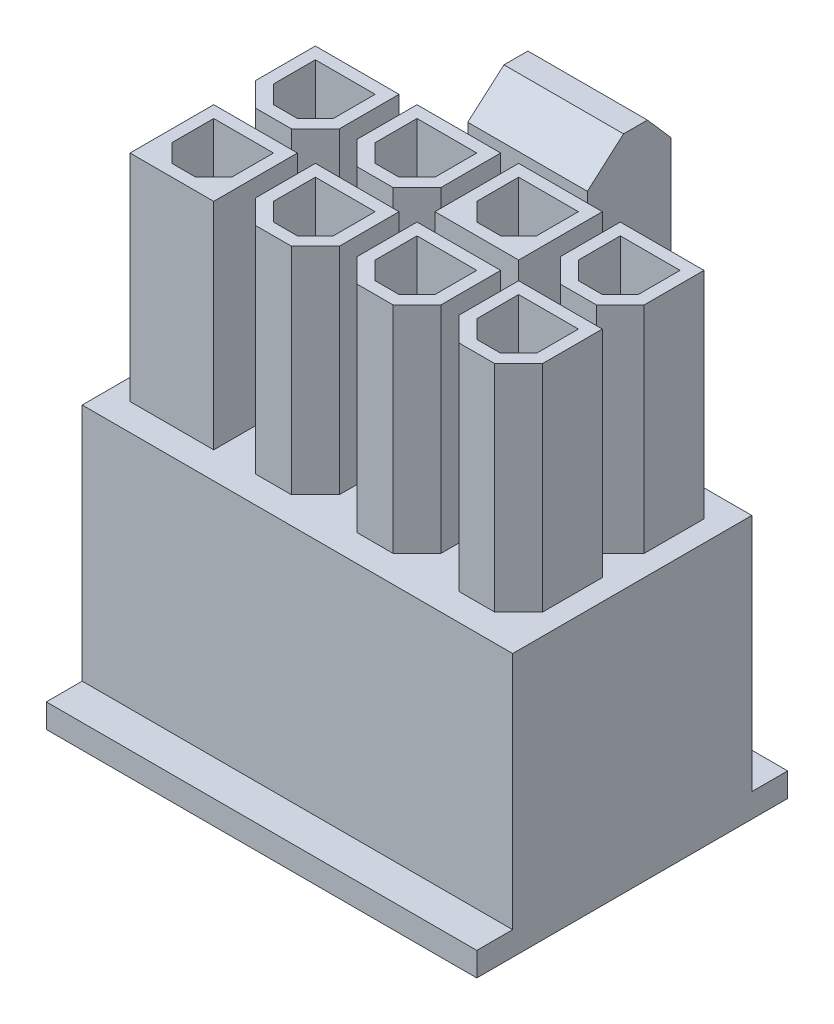
SolidWorks part; units mm, degrees
ref_plane "Ebene vorne" through (0, 0, 0) normal (0, 0, 1) x (1, 0, 0)
ref_plane "Ebene oben" through (0, 0, 0) normal (0, 1, 0) x (1, 0, 0)
ref_plane "Ebene rechts" through (0, 0, 0) normal (1, 0, 0) x (0, 0, -1)
sketch "Skizze1" plane through (0, 0, 0) normal (1, 0, 0) x (0, 0, -1)
  line L1 (5, 0) -> (-5, 0)
  line L2 (5, 0) -> (5, 11)
  line L3 (5, 11) -> (-5, 11)
  line L4 (-5, 0) -> (-5, 11)
  point P4 (0, 0)
  dimension "D1" = 10
  dimension "D2" = 11
extrude "Aufsatz-Linear austragen1" add sketch "Skizze1" along normal mid plane 18
sketch "Skizze2" plane through (0, 0, 0) normal (1, 0, 0) x (0, 0, -1)
  line L0 (0, 0) -> (0, 11) construction
  line L1 (-5, 0) -> (-6.5, 0)
  line L2 (-5, 0) -> (-5, 1)
  line L3 (-5, 1) -> (-6.5, 1)
  line L4 (-6.5, 0) -> (-6.5, 1)
  line L5 (5, 11) -> (-5, 11) construction
  line L6 (6.5, 0) -> (6.5, 1)
  line L7 (5, 1) -> (6.5, 1)
  line L8 (5, 0) -> (5, 1)
  line L9 (5, 0) -> (6.5, 0)
  dimension "D1" = 1.5
  dimension "D2" = 1
extrude "Aufsatz-Linear austragen2" add sketch "Skizze2" along normal mid plane 18
sketch "Skizze3" plane through (0, 0, 0) normal (1, 0, 0) x (0, 0, -1)
  line L0 (5, 11) -> (5.5717, 11)
  line L1 (7.5, 8.198) -> (7.5, 5.198)
  line L2 (7.5, 5.198) -> (8.5, 4)
  line L3 (8.5, 4) -> (8.5, 2)
  line L4 (8.5, 2) -> (6.5, 2)
  line L5 (6.5, 2) -> (6.5, 8)
  line L6 (6.5, 8) -> (5, 8)
  line L7 (5, 1) -> (5, 11) construction
  line L8 (5, 11) -> (5, 8)
  line L9 (-6.5, 0) -> (6.5, 0) construction
  arc A0 (5.5717, 11) -> (6.5359, 9.599) centre (7.0717, 11) ccw
  arc A1 (6.5359, 9.599) -> (7.5, 8.198) centre (6, 8.198) cw
  dimension "D5" = 1.5
  dimension "D1" = 2
  dimension "D2" = 1
  dimension "D3" = 2
  dimension "D4" = 2
  dimension "D6" = 3
  dimension "D7" = 1.5
  dimension "D8" = 3
extrude "Aufsatz-Linear austragen3" add sketch "Skizze3" along normal mid plane 8
sketch "Skizze4" plane through (0, 0, 0) normal (0, -1, 0) x (1, 0, 0)
  line L0 (9, -5) -> (-9, -5) construction
  line L1 (-2.5, -5) -> (2.5, -5)
  line L2 (-2.5, -5) -> (-2.5, -6.5)
  line L3 (-2.5, -6.5) -> (2.5, -6.5)
  line L4 (2.5, -5) -> (2.5, -6.5)
  line L5 (9, -6.5) -> (-9, -6.5) construction
  line L6 (0, -5) -> (0, 0) construction
  line L7 (-4, -6.5) -> (-4, -8.5) construction
  dimension "D1" = 1.5
extrude "Schnitt-Linear austragen1" cut sketch "Skizze4" against normal through all
sketch "Skizze5" plane through (0, 0, 0) normal (1, 0, 0) x (0, 0, -1)
  line L0 (8.1235, 4.451) -> (8.1235, 19.8707)
  line L1 (8.5, 4) -> (7.5, 5.198) construction
  line L2 (8.1235, 19.8707) -> (7.1363, 21)
  line L3 (7.1363, 21) -> (6.1363, 21)
  line L4 (6.1363, 21) -> (4.6235, 19.6776)
  line L5 (4.6235, 19.6776) -> (4.6235, 17.6776)
  line L6 (4.6235, 17.6776) -> (6.1235, 17.6776)
  line L7 (6.1235, 17.6776) -> (6.5, 8)
  line L8 (6.5, 8) -> (6.5, 2)
  line L9 (6.5, 2) -> (8.1235, 4.451)
  line L10 (5, 11) -> (-5, 11) construction
  dimension "D1" = 3.5
  dimension "D2" = 1.5
  dimension "D3" = 1
  dimension "D4" = 10
  dimension "D5" = 2
  dimension "D6" = 2.0093
  dimension "D7" = 1.5
extrude "Aufsatz-Linear austragen4" add sketch "Skizze5" along normal mid plane 5
sketch "Skizze6" plane through (0, 0, 0) normal (0, -1, 0) x (1, 0, 0)
  line L0 (-9, 6.5) -> (-9, -6.5) construction
  line L1 (-8.25, -4) -> (-4.5, -4)
  line L2 (-8.25, -4) -> (-8.25, -0.25)
  line L3 (-8.25, -0.25) -> (-4.5, -0.25)
  line L4 (-4.5, -4) -> (-4.5, -0.25)
  line L5 (-2.5, -5) -> (-9, -5) construction
  dimension "D1" = 0.75
  dimension "D2" = 1
  dimension "D3" = 3.75
extrude "Schnitt-Linear austragen2" cut sketch "Skizze6" against normal blind 10
pattern_linear "Lineares Muster1" count 4 spacing 4.25 along (1, 0, 0) count 2 spacing 4.25 along (0, 0, 1) of "Schnitt-Linear austragen2"
sketch "Skizze7" plane through (0, 11, 0) normal (0, 1, 0) x (1, 0, 0)
  line L1 (-4.5, -0.25) -> (-8.25, -4) construction
  line L2 (-8.25, -0.25) -> (-4.5, -4) construction
  line L4 (-8.125, -0.375) -> (-4.625, -0.375)
  line L6 (-8.125, -0.375) -> (-8.125, -3.875)
  line L8 (-8.125, -3.875) -> (-4.625, -3.875)
  line L10 (-4.625, -0.375) -> (-4.625, -3.875)
  line L11 (-8.125, -0.375) -> (-4.625, -3.875) construction
  point P4 (-6.375, -2.125)
  dimension "D1" = 3.5
extrude "Aufsatz-Linear austragen5" add sketch "Skizze7" along normal blind 9
pattern_linear "Lineares Muster2" count 3 spacing 4.25 along (1, 0, 0) count 2 spacing 4.25 along (0, 0, -1) skipping (0, 1), (1, 0), (1, 1), (2, 0) of "Aufsatz-Linear austragen5"
sketch "Skizze10" plane through (0, 11, 0) normal (0, 1, 0) x (1, 0, 0)
  line L0 (-8.25, 4) -> (-4.5, 0.25) construction
  line L1 (-4.5, 4) -> (-8.25, 0.25) construction
  line L3 (-4.625, 1.375) -> (-5.625, 0.375)
  line L5 (-5.625, 0.375) -> (-7.125, 0.375)
  line L6 (-4.625, 1.375) -> (-4.625, 3.875)
  line L7 (-4.625, 3.875) -> (-8.125, 3.875)
  line L8 (-8.125, 1.375) -> (-8.125, 3.875)
  line L9 (-4.625, 0.375) -> (-8.125, 3.875) construction
  line L10 (-4.625, 3.875) -> (-8.125, 0.375) construction
  line L11 (-7.125, 0.375) -> (-8.125, 1.375)
  point P4 (-6.375, 2.125)
  dimension "D1" = 3.5
extrude "Aufsatz-Linear austragen7" add sketch "Skizze10" along normal up to surface (9 mm away) up to face at (-6.375, 20, 2.125)
pattern_linear "Lineares Muster4" count 4 spacing 4.25 along (1, 0, 0) count 2 spacing 4.25 along (0, 0, 1) skipping (0, 1), (2, 0) of "Aufsatz-Linear austragen7"
sketch "Skizze12" plane through (0, 20, 0) normal (0, 1, 0) x (1, 0, 0)
  line L16 (-8.25, 2.125) -> (-4.5, 2.125) construction
  line L17 (-6.375, 4) -> (-6.375, 0.25) construction
  line L18 (-8.25, 4) -> (-3.0668, -1.1832) construction
  line L19 (-5.875, 0.875) -> (-5.125, 1.625)
  line L20 (-7.625, 3.375) -> (-5.125, 3.375)
  line L21 (-7.625, 3.375) -> (-7.625, 1.625)
  line L22 (-6.875, 0.875) -> (-5.875, 0.875)
  line L23 (-5.125, 3.375) -> (-5.125, 1.625)
  line L24 (-7.625, 3.375) -> (-5.125, 0.875) construction
  line L25 (-7.625, 0.875) -> (-5.125, 3.375) construction
  line L26 (-7.625, 1.625) -> (-6.875, 0.875)
  line L27 (-4.5, 4) -> (-4.5, 0.25) construction
  line L28 (-8.25, 0.25) -> (-8.25, 4) construction
  line L29 (-8.25, 4) -> (-4.5, 4) construction
  line L30 (-4.5, 0.25) -> (-8.25, 0.25) construction
  point P35 (-6.375, 2.125)
  dimension "D1" = 2.5
  dimension "D3" = 0.75
  dimension "D4" = 0.75
  dimension "D5" = 0.75
  dimension "D6" = 0.75
  dimension "D7" = 2.5
extrude "Schnitt-Linear austragen4" cut sketch "Skizze12" against normal through all
pattern_linear "Lineares Muster6" count 4 spacing 4.25 along (1, 0, 0) count 2 spacing 4.25 along (0, 0, 1) of "Schnitt-Linear austragen4"
sketch "草图2" plane through (0, 10, 0) normal (0, -1, 0) x (-1, 0, 0)
  point P8 (-6.375, -2.125)
  point P9 (-6.375, 2.125)
  point P10 (-2.125, 2.125)
  point P11 (-2.125, -2.125)
  point P12 (2.125, -2.125)
  point P13 (2.125, 2.125)
  point P14 (6.375, -2.125)
  point P15 (6.375, 2.125)
other "连接点1" parameters "直径"=2, "端头长度"=10
ref_axis "基准轴9" through (6.375, 0, -2.125) along (0, 1, 0)
other "连接点2" parameters "直径"=2, "端头长度"=10
ref_axis "基准轴10" through (6.375, 0, 2.125) along (0, 1, 0)
other "连接点3" parameters "直径"=2, "端头长度"=10
ref_axis "基准轴11" through (2.125, 0, 2.125) along (0, 1, 0)
other "连接点4" parameters "直径"=2, "端头长度"=10
ref_axis "基准轴12" through (2.125, 0, -2.125) along (0, 1, 0)
other "连接点5" parameters "直径"=2, "端头长度"=10
ref_axis "基准轴13" through (-2.125, 0, -2.125) along (0, 1, 0)
other "连接点6" parameters "直径"=2, "端头长度"=10
ref_axis "基准轴14" through (-2.125, 0, 2.125) along (0, 1, 0)
other "连接点7" parameters "直径"=2, "端头长度"=10
ref_axis "基准轴15" through (-6.375, 0, -2.125) along (0, 1, 0)
other "连接点8" parameters "直径"=2, "端头长度"=10
ref_axis "基准轴16" through (-6.375, 0, 2.125) along (0, 1, 0)
ref_axis "B2" through (6.375, 10, -2.125) along (0, -1, 0)
ref_axis "B3" through (2.125, 10, -2.125) along (0, -1, 0)
ref_axis "B4" through (-2.125, 10, -2.125) along (0, -1, 0)
ref_axis "B5" through (-6.375, 10, -2.125) along (0, -1, 0)
ref_axis "B1" through (6.375, 10, 2.125) along (0, -1, 0)
ref_axis "A1" through (2.125, 10, 2.125) along (0, -1, 0)
ref_axis "A2" through (-2.125, 10, 2.125) along (0, -1, 0)
ref_axis "A3" through (-6.375, 10, 2.125) along (0, -1, 0)
